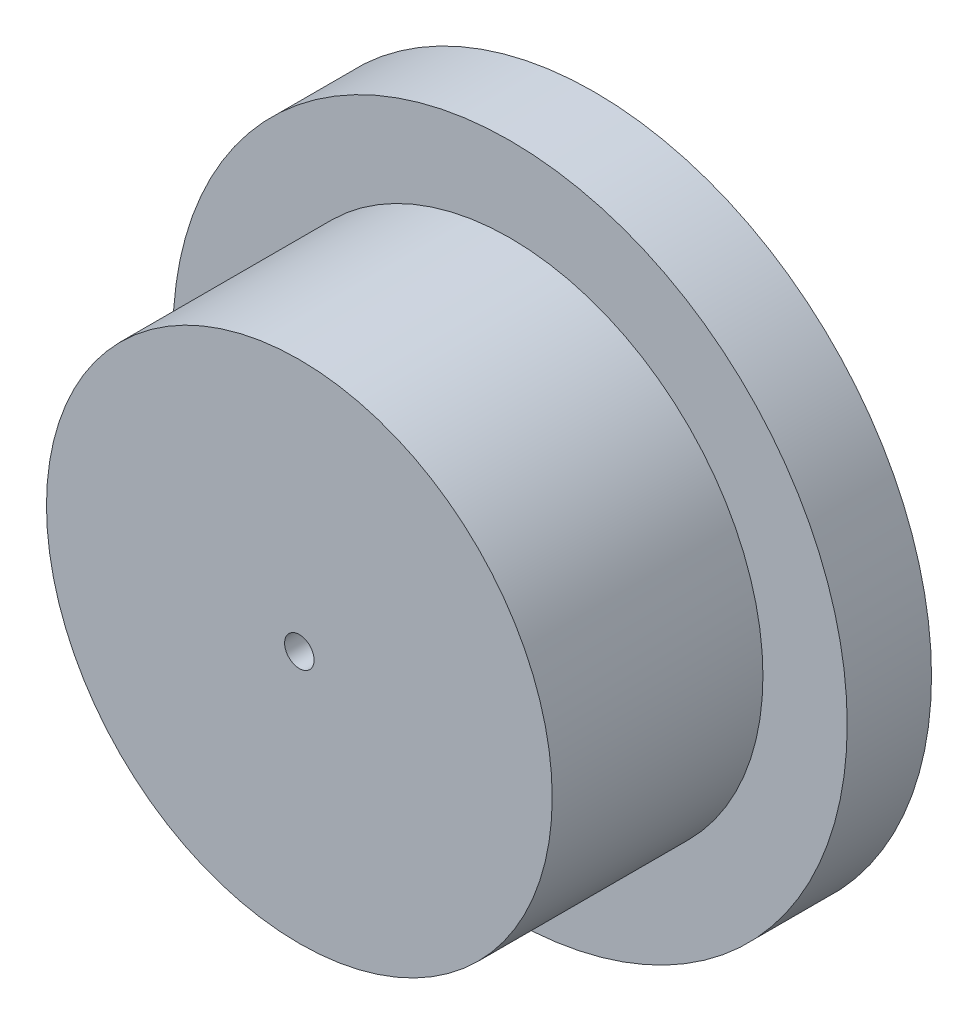
SolidWorks part; units mm, degrees
material "Brass"
ref_plane "Front Plane" through (0, 0, 0) normal (0, 0, 1) x (1, 0, 0)
ref_plane "Top Plane" through (0, 0, 0) normal (0, 1, 0) x (1, 0, 0)
ref_plane "Right Plane" through (0, 0, 0) normal (1, 0, 0) x (0, 0, -1)
sketch "Sketch1" plane through (0, 0, 0) normal (0, 0, 1) x (1, 0, 0)
  circle A0 centre (0, 0) radius 8
extrude "Boss-Extrude1" add sketch "Sketch1" along normal blind 2
sketch "Sketch2" plane through (0, 0, 2) normal (0, 0, 1) x (1, 0, 0)
  circle A0 centre (0, 0) radius 6
  dimension "D1" = 12
extrude "Boss-Extrude2" add sketch "Sketch2" along normal blind 5
sketch "Sketch3" plane through (0, 0, 0) normal (0, 0, -1) x (-1, 0, 0)
  circle A0 centre (0, 0) radius 2
extrude "Cut-Extrude1" cut sketch "Sketch3" against normal blind 2
sketch "Sketch4" plane through (0, 0, 7) normal (0, 0, 1) x (1, 0, 0)
  circle A0 centre (0, 0) radius 0.35
extrude "Cut-Extrude2" cut sketch "Sketch4" against normal through all
chamfer "Chamfer2" distance 2 angle 45 1 edges at (-0.35, 0, 2)
